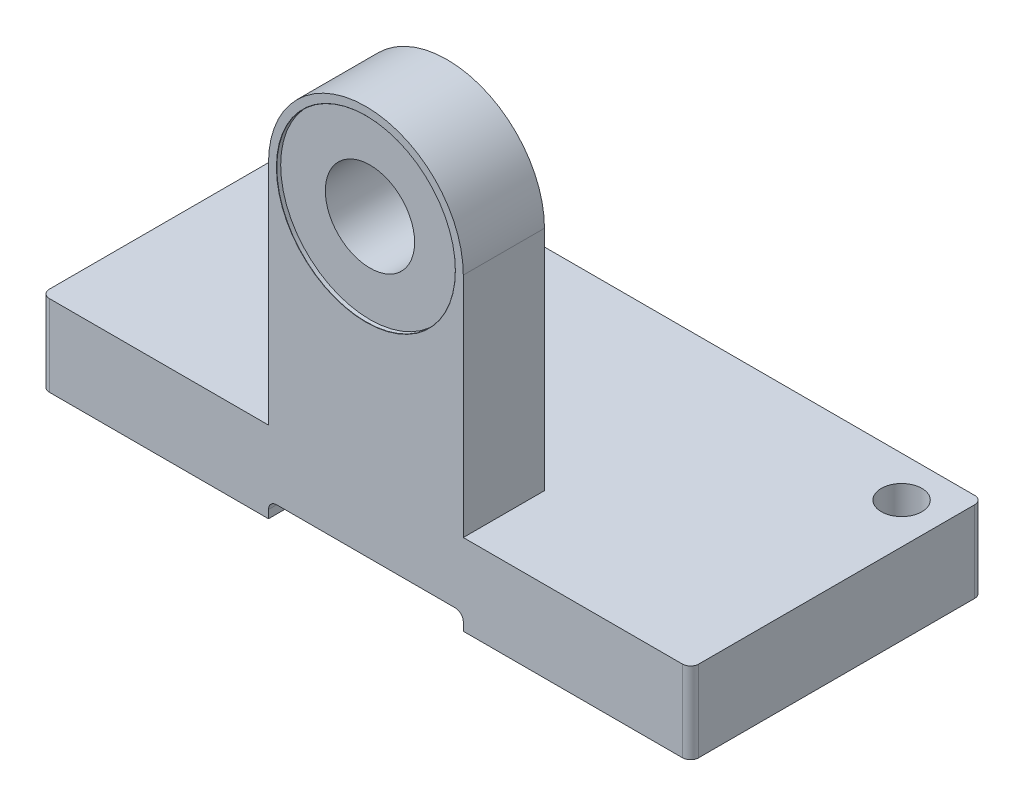
SolidWorks part; units mm, degrees
ref_plane "前视基准面" through (0, 0, 0) normal (0, 0, 1) x (1, 0, 0)
ref_plane "上视基准面" through (0, 0, 0) normal (0, 1, 0) x (1, 0, 0)
ref_plane "右视基准面" through (0, 0, 0) normal (1, 0, 0) x (0, 0, -1)
other "Configuration Table"
sketch "草图1" plane through (0, 0, 0) normal (0, 0, 1) x (1, 0, 0)
  line L1 (0, 0) -> (80, 0)
  line L2 (0, 0) -> (0, -10)
  line L3 (0, -10) -> (80, -10)
  line L4 (80, 0) -> (80, -10)
  dimension "D1" = 80
  dimension "D2" = 10
extrude "凸台-拉伸1" add sketch "草图1" against normal blind 36
sketch "草图2" plane through (0, 0, 0) normal (0, 0, 1) x (1, 0, 0)
  line L0 (28, 0) -> (28, 40)
  line L1 (80, 0) -> (0, 0) construction
  line L2 (28, 40) -> (52, 40)
  line L3 (52, 40) -> (52, 0)
  line L4 (40, -10) -> (40, 46.0142) construction
  line L5 (0, -10) -> (80, -10) construction
  line L6 (80, 0) -> (52, 0)
  line L10 (0, 0) -> (0, -10)
  line L11 (0, -10) -> (80, -10)
  line L12 (80, -10) -> (80, 0)
  line L13 (80, 0) -> (0, 0)
  line L14 (0, 0) -> (0, -10)
  line L15 (0, -10) -> (80, -10)
  line L16 (80, -10) -> (80, 0)
  line L17 (28, 0) -> (0, 0)
  point P12 (0, 0)
  dimension "D1" = 40
  dimension "D2" = 24
  dimension "D3" = 12
  dimension "D4" = 0
extrude "凸台-拉伸3" add sketch "草图2" against normal blind 10
fillet "圆角1" 2 edges at (52, 40, -5) (28, 40, -5) type full round first side face at (52, 20, -5) second side face at (28, 20, -5) middle face at (40, 40, -5)
sketch "草图3" plane through (0, 0, 0) normal (0, 0, 1) x (1, 0, 0)
  line L0 (28, 0) -> (28, -12.8067) construction
  line L1 (52, 0) -> (52, -16) construction
  line L2 (0, -10) -> (80, -10) construction
  line L3 (28, -10) -> (52, -10)
  line L4 (28, -10) -> (28, -8)
  line L5 (28, -8) -> (52, -8)
  line L6 (52, -10) -> (52, -8)
  dimension "D1" = 2
extrude "切除-拉伸1" cut sketch "草图3" against normal through all
hole_wizard "M10 六角头螺栓C级的柱形沉头孔1" positions "3D草图2" profile "草图5" counterbore size "M10" standard "GB" end condition through all
sketch3d "3D草图2"
  line L0 (40, 28, -10) -> (40, 28, 0) construction
  point P0 (40, 28, 0)
sketch "草图5" plane through (40, 28, 0) normal (1, 0, 0) x (0, -1, 0)
  line L0 (0, 0) -> (0, 36)
  line L1 (0, 36) -> (5.5, 36)
  line L3 (5.5, 36) -> (5.5, 0.5)
  line L4 (11, 0.5) -> (5.5, 0.5)
  line L5 (11, 0.5) -> (11, 0.021)
  line L6 (11, 0.021) -> (11.025, 0)
  line L7 (11.025, 0) -> (0, 0)
  line L8 (-11, 0.021) -> (-11.025, 0) construction
  line L11 (0, -6.35) -> (0, 107.95) construction
  dimension "通孔孔直径" = 11
  dimension "通孔孔深度" = 36
  dimension "柱形沉头孔直径" = 22
  dimension "柱形沉头孔深度" = 0.5
  dimension "近端锥形沉头孔直径" = 22.05
  dimension "近端锥形沉头孔角度" = 100
sketch "草图6" plane through (0, 0, 0) normal (0, 1, 0) x (1, 0, 0)
  line L0 (80, 36) -> (0, 36) construction
  line L1 (40, 36) -> (40, -2.7819) construction
  circle A0 centre (75, 31) radius 2.5
  circle A1 centre (5, 31) radius 2.5
  dimension "D1" = 5
  dimension "D3" = 5
  dimension "D2" = 5
  dimension "D4" = 5
  dimension "D5" = 35
  dimension "D6" = 35
extrude "切除-拉伸2" cut sketch "草图6" against normal through all
fillet "圆角2" radius 1 6 edges at (0, -5, -36) (80, -5, -36) (80, -5, 0) (0, -5, 0) (28, -8, -18) (52, -8, -18)
